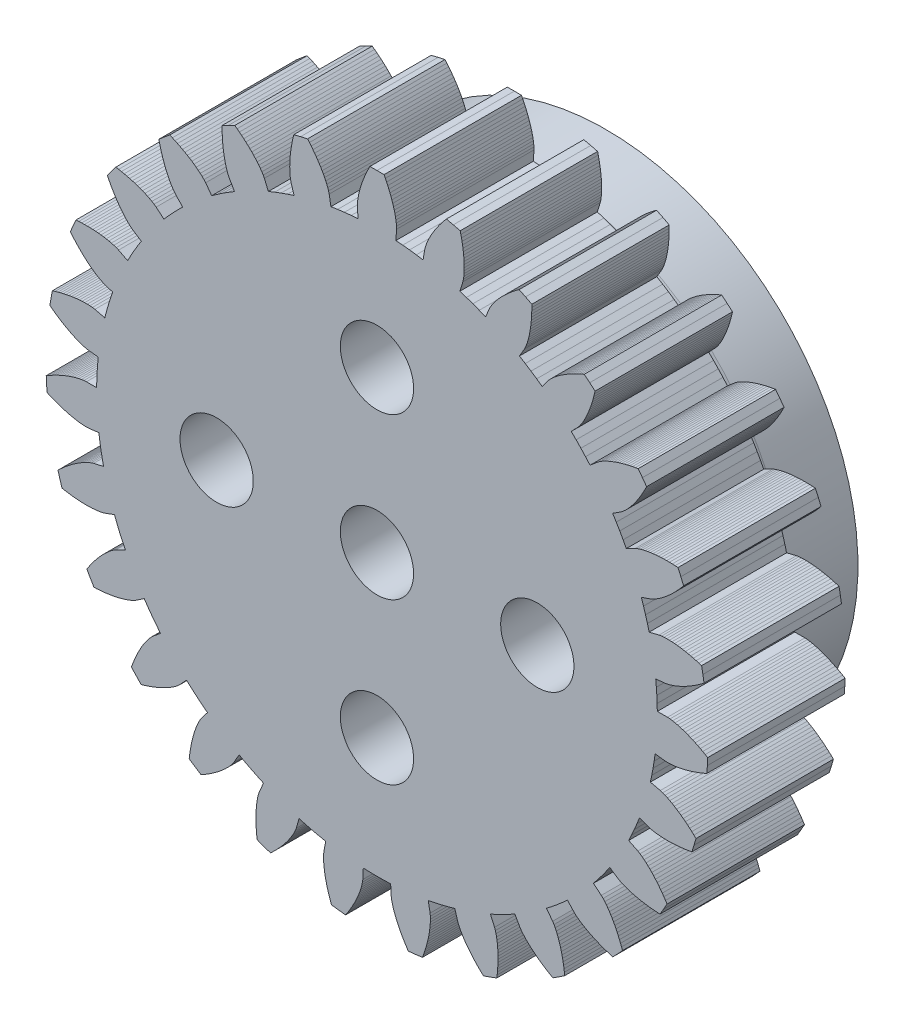
SolidWorks part; units mm, degrees
ref_plane "前视基准面" through (0, 0, 0) normal (0, 0, 1) x (1, 0, 0)
ref_plane "上视基准面" through (0, 0, 0) normal (0, 1, 0) x (1, 0, 0)
ref_plane "右视基准面" through (0, 0, 0) normal (1, 0, 0) x (0, 0, -1)
other "Configuration Table"
sketch "Module 1, 27 teeth, 20 degree pressure angle profile" plane through (0, 0, 0) normal (0, 0, 1) x (1, 0, 0)
  line L0 (1.421, 12.1572) -> (1.1238, 12.1883)
  line L1 (1.1238, 12.1883) -> (0.8259, 12.2121)
  line L2 (0.8259, 12.2121) -> (0.856, 12.6569)
  line L3 (0.856, 12.6569) -> (0.8537, 12.7676)
  line L4 (0.8537, 12.7676) -> (0.8432, 12.8788)
  line L5 (0.8432, 12.8788) -> (0.8273, 12.9903)
  line L6 (0.8273, 12.9903) -> (0.8069, 13.1021)
  line L7 (0.8069, 13.1021) -> (0.7825, 13.214)
  line L8 (0.7825, 13.214) -> (0.7544, 13.3261)
  line L9 (0.7544, 13.3261) -> (0.723, 13.4382)
  line L10 (0.723, 13.4382) -> (0.6884, 13.5505)
  line L11 (0.6884, 13.5505) -> (0.6507, 13.6627)
  line L12 (0.6507, 13.6627) -> (0.6101, 13.7749)
  line L13 (0.6101, 13.7749) -> (0.5666, 13.8871)
  line L14 (0.5666, 13.8871) -> (0.5205, 13.9993)
  line L15 (0.5205, 13.9993) -> (0.4716, 14.1113)
  line L16 (0.4716, 14.1113) -> (0.4202, 14.2233)
  line L17 (0.4202, 14.2233) -> (0.3662, 14.3351)
  line L18 (0.3662, 14.3351) -> (0.3096, 14.4467)
  line L19 (0.3096, 14.4467) -> (0, 14.45)
  line L20 (0, 14.45) -> (-0.3096, 14.4467)
  line L21 (-0.3096, 14.4467) -> (-0.3662, 14.3351)
  line L22 (-0.3662, 14.3351) -> (-0.4202, 14.2233)
  line L23 (-0.4202, 14.2233) -> (-0.4716, 14.1113)
  line L24 (-0.4716, 14.1113) -> (-0.5205, 13.9993)
  line L25 (-0.5205, 13.9993) -> (-0.5666, 13.8871)
  line L26 (-0.5666, 13.8871) -> (-0.6101, 13.7749)
  line L27 (-0.6101, 13.7749) -> (-0.6507, 13.6627)
  line L28 (-0.6507, 13.6627) -> (-0.6884, 13.5505)
  line L29 (-0.6884, 13.5505) -> (-0.723, 13.4382)
  line L30 (-0.723, 13.4382) -> (-0.7544, 13.3261)
  line L31 (-0.7544, 13.3261) -> (-0.7825, 13.214)
  line L32 (-0.7825, 13.214) -> (-0.8069, 13.1021)
  line L33 (-0.8069, 13.1021) -> (-0.8273, 12.9903)
  line L34 (-0.8273, 12.9903) -> (-0.8432, 12.8788)
  line L35 (-0.8432, 12.8788) -> (-0.8537, 12.7676)
  line L36 (-0.8537, 12.7676) -> (-0.856, 12.6569)
  line L37 (-0.856, 12.6569) -> (-0.8259, 12.2121)
  line L38 (-0.8259, 12.2121) -> (-1.1238, 12.1883)
  line L39 (-1.1238, 12.1883) -> (-1.421, 12.1572)
  line L40 (-1.421, 12.1572) -> (-1.7173, 12.1189)
  line L41 (-1.7173, 12.1189) -> (-2.0127, 12.0734)
  line L42 (-2.0127, 12.0734) -> (-2.086, 12.5132)
  line L43 (-2.086, 12.5132) -> (-2.1137, 12.6203)
  line L44 (-2.1137, 12.6203) -> (-2.1495, 12.7261)
  line L45 (-2.1495, 12.7261) -> (-2.1907, 12.831)
  line L46 (-2.1907, 12.831) -> (-2.2364, 12.935)
  line L47 (-2.2364, 12.935) -> (-2.286, 13.0383)
  line L48 (-2.286, 13.0383) -> (-2.3391, 13.1408)
  line L49 (-2.3391, 13.1408) -> (-2.3956, 13.2427)
  line L50 (-2.3956, 13.2427) -> (-2.4551, 13.3439)
  line L51 (-2.4551, 13.3439) -> (-2.5177, 13.4445)
  line L52 (-2.5177, 13.4445) -> (-2.5831, 13.5443)
  line L53 (-2.5831, 13.5443) -> (-2.6512, 13.6435)
  line L54 (-2.6512, 13.6435) -> (-2.722, 13.742)
  line L55 (-2.722, 13.742) -> (-2.7954, 13.8397)
  line L56 (-2.7954, 13.8397) -> (-2.8713, 13.9368)
  line L57 (-2.8713, 13.9368) -> (-2.9496, 14.0331)
  line L58 (-2.9496, 14.0331) -> (-3.0303, 14.1287)
  line L59 (-3.0303, 14.1287) -> (-3.3324, 14.0605)
  line L60 (-3.3324, 14.0605) -> (-3.6329, 13.9859)
  line L61 (-3.6329, 13.9859) -> (-3.6622, 13.8642)
  line L62 (-3.6622, 13.8642) -> (-3.689, 13.743)
  line L63 (-3.689, 13.743) -> (-3.7132, 13.6222)
  line L64 (-3.7132, 13.6222) -> (-3.7349, 13.5019)
  line L65 (-3.7349, 13.5019) -> (-3.754, 13.3821)
  line L66 (-3.754, 13.3821) -> (-3.7704, 13.2629)
  line L67 (-3.7704, 13.2629) -> (-3.784, 13.1444)
  line L68 (-3.784, 13.1444) -> (-3.7948, 13.0264)
  line L69 (-3.7948, 13.0264) -> (-3.8026, 12.9093)
  line L70 (-3.8026, 12.9093) -> (-3.8073, 12.7929)
  line L71 (-3.8073, 12.7929) -> (-3.8088, 12.6774)
  line L72 (-3.8088, 12.6774) -> (-3.8067, 12.5628)
  line L73 (-3.8067, 12.5628) -> (-3.8008, 12.4494)
  line L74 (-3.8008, 12.4494) -> (-3.7906, 12.3372)
  line L75 (-3.7906, 12.3372) -> (-3.7751, 12.2266)
  line L76 (-3.7751, 12.2266) -> (-3.7518, 12.1184)
  line L77 (-3.7518, 12.1184) -> (-3.6199, 11.6925)
  line L78 (-3.6199, 11.6925) -> (-3.9043, 11.6006)
  line L79 (-3.9043, 11.6006) -> (-4.1863, 11.5018)
  line L80 (-4.1863, 11.5018) -> (-4.4659, 11.3962)
  line L81 (-4.4659, 11.3962) -> (-4.7427, 11.2838)
  line L82 (-4.7427, 11.2838) -> (-4.9155, 11.6948)
  line L83 (-4.9155, 11.6948) -> (-4.9672, 11.7927)
  line L84 (-4.9672, 11.7927) -> (-5.0264, 11.8874)
  line L85 (-5.0264, 11.8874) -> (-5.0907, 11.9799)
  line L86 (-5.0907, 11.9799) -> (-5.1591, 12.0706)
  line L87 (-5.1591, 12.0706) -> (-5.2312, 12.1596)
  line L88 (-5.2312, 12.1596) -> (-5.3065, 12.2472)
  line L89 (-5.3065, 12.2472) -> (-5.385, 12.3333)
  line L90 (-5.385, 12.3333) -> (-5.4663, 12.4181)
  line L91 (-5.4663, 12.4181) -> (-5.5503, 12.5015)
  line L92 (-5.5503, 12.5015) -> (-5.637, 12.5835)
  line L93 (-5.637, 12.5835) -> (-5.7262, 12.6643)
  line L94 (-5.7262, 12.6643) -> (-5.8178, 12.7438)
  line L95 (-5.8178, 12.7438) -> (-5.9117, 12.822)
  line L96 (-5.9117, 12.822) -> (-6.0079, 12.899)
  line L97 (-6.0079, 12.899) -> (-6.1064, 12.9746)
  line L98 (-6.1064, 12.9746) -> (-6.207, 13.049)
  line L99 (-6.207, 13.049) -> (-6.4851, 12.913)
  line L100 (-6.4851, 12.913) -> (-6.7604, 12.7711)
  line L101 (-6.7604, 12.7711) -> (-6.7608, 12.646)
  line L102 (-6.7608, 12.646) -> (-6.7589, 12.5218)
  line L103 (-6.7589, 12.5218) -> (-6.7546, 12.3987)
  line L104 (-6.7546, 12.3987) -> (-6.748, 12.2766)
  line L105 (-6.748, 12.2766) -> (-6.7389, 12.1557)
  line L106 (-6.7389, 12.1557) -> (-6.7274, 12.0359)
  line L107 (-6.7274, 12.0359) -> (-6.7133, 11.9174)
  line L108 (-6.7133, 11.9174) -> (-6.6966, 11.8002)
  line L109 (-6.6966, 11.8002) -> (-6.6772, 11.6844)
  line L110 (-6.6772, 11.6844) -> (-6.6549, 11.57)
  line L111 (-6.6549, 11.57) -> (-6.6297, 11.4573)
  line L112 (-6.6297, 11.4573) -> (-6.6013, 11.3463)
  line L113 (-6.6013, 11.3463) -> (-6.5694, 11.2373)
  line L114 (-6.5694, 11.2373) -> (-6.5335, 11.1305)
  line L115 (-6.5335, 11.1305) -> (-6.493, 11.0264)
  line L116 (-6.493, 11.0264) -> (-6.4454, 10.9265)
  line L117 (-6.4454, 10.9265) -> (-6.2188, 10.5425)
  line L118 (-6.2188, 10.5425) -> (-6.4743, 10.3875)
  line L119 (-6.4743, 10.3875) -> (-6.726, 10.2264)
  line L120 (-6.726, 10.2264) -> (-6.9736, 10.0591)
  line L121 (-6.9736, 10.0591) -> (-7.2171, 9.8859)
  line L122 (-7.2171, 9.8859) -> (-7.48, 10.246)
  line L123 (-7.48, 10.246) -> (-7.5529, 10.3293)
  line L124 (-7.5529, 10.3293) -> (-7.6324, 10.4078)
  line L125 (-7.6324, 10.4078) -> (-7.7162, 10.483)
  line L126 (-7.7162, 10.483) -> (-7.8037, 10.5554)
  line L127 (-7.8037, 10.5554) -> (-7.8944, 10.6255)
  line L128 (-7.8944, 10.6255) -> (-7.9879, 10.6933)
  line L129 (-7.9879, 10.6933) -> (-8.0841, 10.759)
  line L130 (-8.0841, 10.759) -> (-8.1827, 10.8227)
  line L131 (-8.1827, 10.8227) -> (-8.2838, 10.8845)
  line L132 (-8.2838, 10.8845) -> (-8.387, 10.9444)
  line L133 (-8.387, 10.9444) -> (-8.4924, 11.0024)
  line L134 (-8.4924, 11.0024) -> (-8.5999, 11.0586)
  line L135 (-8.5999, 11.0586) -> (-8.7093, 11.1131)
  line L136 (-8.7093, 11.1131) -> (-8.8207, 11.1657)
  line L137 (-8.8207, 11.1657) -> (-8.9339, 11.2167)
  line L138 (-8.9339, 11.2167) -> (-9.049, 11.2658)
  line L139 (-9.049, 11.2658) -> (-9.2883, 11.0693)
  line L140 (-9.2883, 11.0693) -> (-9.5233, 10.8678)
  line L141 (-9.5233, 10.8678) -> (-9.4949, 10.7459)
  line L142 (-9.4949, 10.7459) -> (-9.4644, 10.6256)
  line L143 (-9.4644, 10.6256) -> (-9.4319, 10.5068)
  line L144 (-9.4319, 10.5068) -> (-9.3973, 10.3895)
  line L145 (-9.3973, 10.3895) -> (-9.3606, 10.2739)
  line L146 (-9.3606, 10.2739) -> (-9.3217, 10.1601)
  line L147 (-9.3217, 10.1601) -> (-9.2807, 10.048)
  line L148 (-9.2807, 10.048) -> (-9.2374, 9.9378)
  line L149 (-9.2374, 9.9378) -> (-9.1918, 9.8295)
  line L150 (-9.1918, 9.8295) -> (-9.1438, 9.7234)
  line L151 (-9.1438, 9.7234) -> (-9.0932, 9.6195)
  line L152 (-9.0932, 9.6195) -> (-9.04, 9.5181)
  line L153 (-9.04, 9.5181) -> (-8.9838, 9.4194)
  line L154 (-8.9838, 9.4194) -> (-8.9243, 9.3237)
  line L155 (-8.9243, 9.3237) -> (-8.8608, 9.2318)
  line L156 (-8.8608, 9.2318) -> (-8.7914, 9.1456)
  line L157 (-8.7914, 9.1456) -> (-8.4825, 8.8241)
  line L158 (-8.4825, 8.8241) -> (-8.6953, 8.6144)
  line L159 (-8.6953, 8.6144) -> (-8.9031, 8.3996)
  line L160 (-8.9031, 8.3996) -> (-9.1055, 8.1798)
  line L161 (-9.1055, 8.1798) -> (-9.3024, 7.955)
  line L162 (-9.3024, 7.955) -> (-9.6413, 8.2448)
  line L163 (-9.6413, 8.2448) -> (-9.7314, 8.3091)
  line L164 (-9.7314, 8.3091) -> (-9.8268, 8.3671)
  line L165 (-9.8268, 8.3671) -> (-9.9258, 8.4209)
  line L166 (-9.9258, 8.4209) -> (-10.0276, 8.4712)
  line L167 (-10.0276, 8.4712) -> (-10.132, 8.5185)
  line L168 (-10.132, 8.5185) -> (-10.2386, 8.5629)
  line L169 (-10.2386, 8.5629) -> (-10.3474, 8.6047)
  line L170 (-10.3474, 8.6047) -> (-10.4581, 8.6439)
  line L171 (-10.4581, 8.6439) -> (-10.5706, 8.6807)
  line L172 (-10.5706, 8.6807) -> (-10.6849, 8.7152)
  line L173 (-10.6849, 8.7152) -> (-10.8008, 8.7474)
  line L174 (-10.8008, 8.7474) -> (-10.9184, 8.7773)
  line L175 (-10.9184, 8.7773) -> (-11.0374, 8.805)
  line L176 (-11.0374, 8.805) -> (-11.1579, 8.8306)
  line L177 (-11.1579, 8.8306) -> (-11.2798, 8.854)
  line L178 (-11.2798, 8.854) -> (-11.4031, 8.8753)
  line L179 (-11.4031, 8.8753) -> (-11.5907, 8.6289)
  line L180 (-11.5907, 8.6289) -> (-11.7729, 8.3786)
  line L181 (-11.7729, 8.3786) -> (-11.7171, 8.2666)
  line L182 (-11.7171, 8.2666) -> (-11.6597, 8.1565)
  line L183 (-11.6597, 8.1565) -> (-11.6007, 8.0484)
  line L184 (-11.6007, 8.0484) -> (-11.54, 7.9423)
  line L185 (-11.54, 7.9423) -> (-11.4776, 7.8383)
  line L186 (-11.4776, 7.8383) -> (-11.4135, 7.7365)
  line L187 (-11.4135, 7.7365) -> (-11.3477, 7.6369)
  line L188 (-11.3477, 7.6369) -> (-11.2802, 7.5396)
  line L189 (-11.2802, 7.5396) -> (-11.2109, 7.4448)
  line L190 (-11.2109, 7.4448) -> (-11.1397, 7.3526)
  line L191 (-11.1397, 7.3526) -> (-11.0665, 7.2632)
  line L192 (-11.0665, 7.2632) -> (-10.9913, 7.1768)
  line L193 (-10.9913, 7.1768) -> (-10.9139, 7.0937)
  line L194 (-10.9139, 7.0937) -> (-10.8339, 7.0143)
  line L195 (-10.8339, 7.0143) -> (-10.751, 6.9395)
  line L196 (-10.751, 6.9395) -> (-10.6636, 6.8716)
  line L197 (-10.6636, 6.8716) -> (-10.2888, 6.6301)
  line L198 (-10.2888, 6.6301) -> (-10.4476, 6.3769)
  line L199 (-10.4476, 6.3769) -> (-10.6002, 6.12)
  line L200 (-10.6002, 6.12) -> (-10.7464, 5.8594)
  line L201 (-10.7464, 5.8594) -> (-10.8862, 5.5953)
  line L202 (-10.8862, 5.5953) -> (-11.2828, 5.7991)
  line L203 (-11.2828, 5.7991) -> (-11.3853, 5.8409)
  line L204 (-11.3853, 5.8409) -> (-11.4915, 5.8753)
  line L205 (-11.4915, 5.8753) -> (-11.6002, 5.9049)
  line L206 (-11.6002, 5.9049) -> (-11.7109, 5.9304)
  line L207 (-11.7109, 5.9304) -> (-11.8234, 5.9523)
  line L208 (-11.8234, 5.9523) -> (-11.9374, 5.9709)
  line L209 (-11.9374, 5.9709) -> (-12.0528, 5.9865)
  line L210 (-12.0528, 5.9865) -> (-12.1696, 5.9991)
  line L211 (-12.1696, 5.9991) -> (-12.2876, 6.009)
  line L212 (-12.2876, 6.009) -> (-12.4067, 6.0162)
  line L213 (-12.4067, 6.0162) -> (-12.527, 6.0207)
  line L214 (-12.527, 6.0207) -> (-12.6482, 6.0227)
  line L215 (-12.6482, 6.0227) -> (-12.7705, 6.0223)
  line L216 (-12.7705, 6.0223) -> (-12.8936, 6.0194)
  line L217 (-12.8936, 6.0194) -> (-13.0177, 6.014)
  line L218 (-13.0177, 6.014) -> (-13.1425, 6.0064)
  line L219 (-13.1425, 6.0064) -> (-13.2682, 5.7234)
  line L220 (-13.2682, 5.7234) -> (-13.3878, 5.4377)
  line L221 (-13.3878, 5.4377) -> (-13.3077, 5.3416)
  line L222 (-13.3077, 5.3416) -> (-13.2265, 5.2477)
  line L223 (-13.2265, 5.2477) -> (-13.1441, 5.1562)
  line L224 (-13.1441, 5.1562) -> (-13.0605, 5.0669)
  line L225 (-13.0605, 5.0669) -> (-12.9758, 4.9801)
  line L226 (-12.9758, 4.9801) -> (-12.89, 4.8958)
  line L227 (-12.89, 4.8958) -> (-12.803, 4.814)
  line L228 (-12.803, 4.814) -> (-12.7149, 4.735)
  line L229 (-12.7149, 4.735) -> (-12.6256, 4.6587)
  line L230 (-12.6256, 4.6587) -> (-12.535, 4.5855)
  line L231 (-12.535, 4.5855) -> (-12.4432, 4.5153)
  line L232 (-12.4432, 4.5153) -> (-12.3501, 4.4486)
  line L233 (-12.3501, 4.4486) -> (-12.2556, 4.3855)
  line L234 (-12.2556, 4.3855) -> (-12.1595, 4.3267)
  line L235 (-12.1595, 4.3267) -> (-12.0616, 4.2731)
  line L236 (-12.0616, 4.2731) -> (-11.9608, 4.2272)
  line L237 (-11.9608, 4.2272) -> (-11.5405, 4.0786)
  line L238 (-11.5405, 4.0786) -> (-11.6366, 3.7957)
  line L239 (-11.6366, 3.7957) -> (-11.7258, 3.5105)
  line L240 (-11.7258, 3.5105) -> (-11.808, 3.2232)
  line L241 (-11.808, 3.2232) -> (-11.8832, 2.934)
  line L242 (-11.8832, 2.934) -> (-12.316, 3.0408)
  line L243 (-12.316, 3.0408) -> (-12.4254, 3.0578)
  line L244 (-12.4254, 3.0578) -> (-12.5367, 3.0668)
  line L245 (-12.5367, 3.0668) -> (-12.6493, 3.0705)
  line L246 (-12.6493, 3.0705) -> (-12.7629, 3.0698)
  line L247 (-12.7629, 3.0698) -> (-12.8774, 3.0652)
  line L248 (-12.8774, 3.0652) -> (-12.9926, 3.057)
  line L249 (-12.9926, 3.057) -> (-13.1085, 3.0455)
  line L250 (-13.1085, 3.0455) -> (-13.2251, 3.0309)
  line L251 (-13.2251, 3.0309) -> (-13.3421, 3.0133)
  line L252 (-13.3421, 3.0133) -> (-13.4597, 2.9928)
  line L253 (-13.4597, 2.9928) -> (-13.5778, 2.9695)
  line L254 (-13.5778, 2.9695) -> (-13.6962, 2.9435)
  line L255 (-13.6962, 2.9435) -> (-13.8151, 2.9149)
  line L256 (-13.8151, 2.9149) -> (-13.9342, 2.8836)
  line L257 (-13.9342, 2.8836) -> (-14.0537, 2.8499)
  line L258 (-14.0537, 2.8499) -> (-14.1734, 2.8136)
  line L259 (-14.1734, 2.8136) -> (-14.2305, 2.5092)
  line L260 (-14.2305, 2.5092) -> (-14.281, 2.2037)
  line L261 (-14.281, 2.2037) -> (-14.1809, 2.1287)
  line L262 (-14.1809, 2.1287) -> (-14.0802, 2.0561)
  line L263 (-14.0802, 2.0561) -> (-13.9789, 1.9859)
  line L264 (-13.9789, 1.9859) -> (-13.877, 1.9184)
  line L265 (-13.877, 1.9184) -> (-13.7746, 1.8534)
  line L266 (-13.7746, 1.8534) -> (-13.6716, 1.7912)
  line L267 (-13.6716, 1.7912) -> (-13.5681, 1.7317)
  line L268 (-13.5681, 1.7317) -> (-13.4641, 1.6751)
  line L269 (-13.4641, 1.6751) -> (-13.3596, 1.6215)
  line L270 (-13.3596, 1.6215) -> (-13.2546, 1.5711)
  line L271 (-13.2546, 1.5711) -> (-13.1491, 1.524)
  line L272 (-13.1491, 1.524) -> (-13.0431, 1.4805)
  line L273 (-13.0431, 1.4805) -> (-12.9366, 1.441)
  line L274 (-12.9366, 1.441) -> (-12.8296, 1.4059)
  line L275 (-12.8296, 1.4059) -> (-12.7219, 1.3763)
  line L276 (-12.7219, 1.3763) -> (-12.6133, 1.3549)
  line L277 (-12.6133, 1.3549) -> (-12.17, 1.3073)
  line L278 (-12.17, 1.3073) -> (-12.1983, 1.0098)
  line L279 (-12.1983, 1.0098) -> (-12.2193, 0.7117)
  line L280 (-12.2193, 0.7117) -> (-12.233, 0.4132)
  line L281 (-12.233, 0.4132) -> (-12.2395, 0.1144)
  line L282 (-12.2395, 0.1144) -> (-12.6853, 0.1186)
  line L283 (-12.6853, 0.1186) -> (-12.7956, 0.1099)
  line L284 (-12.7956, 0.1099) -> (-12.906, 0.093)
  line L285 (-12.906, 0.093) -> (-13.0164, 0.0706)
  line L286 (-13.0164, 0.0706) -> (-13.1268, 0.0437)
  line L287 (-13.1268, 0.0437) -> (-13.2371, 0.0128)
  line L288 (-13.2371, 0.0128) -> (-13.3474, -0.0217)
  line L289 (-13.3474, -0.0217) -> (-13.4575, -0.0596)
  line L290 (-13.4575, -0.0596) -> (-13.5676, -0.1007)
  line L291 (-13.5676, -0.1007) -> (-13.6774, -0.1448)
  line L292 (-13.6774, -0.1448) -> (-13.7871, -0.1919)
  line L293 (-13.7871, -0.1919) -> (-13.8966, -0.2418)
  line L294 (-13.8966, -0.2418) -> (-14.0059, -0.2944)
  line L295 (-14.0059, -0.2944) -> (-14.1149, -0.3497)
  line L296 (-14.1149, -0.3497) -> (-14.2236, -0.4076)
  line L297 (-14.2236, -0.4076) -> (-14.3321, -0.468)
  line L298 (-14.3321, -0.468) -> (-14.4402, -0.5309)
  line L299 (-14.4402, -0.5309) -> (-14.4256, -0.8402)
  line L300 (-14.4256, -0.8402) -> (-14.4042, -1.1491)
  line L301 (-14.4042, -1.1491) -> (-14.2895, -1.199)
  line L302 (-14.2895, -1.199) -> (-14.1748, -1.2465)
  line L303 (-14.1748, -1.2465) -> (-14.06, -1.2913)
  line L304 (-14.06, -1.2913) -> (-13.9453, -1.3336)
  line L305 (-13.9453, -1.3336) -> (-13.8307, -1.3732)
  line L306 (-13.8307, -1.3732) -> (-13.7162, -1.41)
  line L307 (-13.7162, -1.41) -> (-13.6017, -1.444)
  line L308 (-13.6017, -1.444) -> (-13.4875, -1.4751)
  line L309 (-13.4875, -1.4751) -> (-13.3735, -1.5031)
  line L310 (-13.3735, -1.5031) -> (-13.2597, -1.528)
  line L311 (-13.2597, -1.528) -> (-13.1461, -1.5495)
  line L312 (-13.1461, -1.5495) -> (-13.033, -1.5674)
  line L313 (-13.033, -1.5674) -> (-12.9202, -1.5813)
  line L314 (-12.9202, -1.5813) -> (-12.808, -1.5907)
  line L315 (-12.808, -1.5907) -> (-12.6964, -1.5946)
  line L316 (-12.6964, -1.5946) -> (-12.5858, -1.5905)
  line L317 (-12.5858, -1.5905) -> (-12.1434, -1.5346)
  line L318 (-12.1434, -1.5346) -> (-12.1023, -1.8306)
  line L319 (-12.1023, -1.8306) -> (-12.054, -2.1255)
  line L320 (-12.054, -2.1255) -> (-11.9986, -2.4191)
  line L321 (-11.9986, -2.4191) -> (-11.9359, -2.7113)
  line L322 (-11.9359, -2.7113) -> (-12.3707, -2.81)
  line L323 (-12.3707, -2.81) -> (-12.4761, -2.8439)
  line L324 (-12.4761, -2.8439) -> (-12.5796, -2.8859)
  line L325 (-12.5796, -2.8859) -> (-12.6819, -2.9331)
  line L326 (-12.6819, -2.9331) -> (-12.7831, -2.9847)
  line L327 (-12.7831, -2.9847) -> (-12.8833, -3.0402)
  line L328 (-12.8833, -3.0402) -> (-12.9826, -3.0992)
  line L329 (-12.9826, -3.0992) -> (-13.081, -3.1615)
  line L330 (-13.081, -3.1615) -> (-13.1786, -3.2269)
  line L331 (-13.1786, -3.2269) -> (-13.2753, -3.2952)
  line L332 (-13.2753, -3.2952) -> (-13.3712, -3.3662)
  line L333 (-13.3712, -3.3662) -> (-13.4663, -3.44)
  line L334 (-13.4663, -3.44) -> (-13.5604, -3.5164)
  line L335 (-13.5604, -3.5164) -> (-13.6538, -3.5954)
  line L336 (-13.6538, -3.5954) -> (-13.7463, -3.6768)
  line L337 (-13.7463, -3.6768) -> (-13.8379, -3.7606)
  line L338 (-13.8379, -3.7606) -> (-13.9286, -3.8467)
  line L339 (-13.9286, -3.8467) -> (-13.8429, -4.1443)
  line L340 (-13.8429, -4.1443) -> (-13.751, -4.44)
  line L341 (-13.751, -4.44) -> (-13.6278, -4.4621)
  line L342 (-13.6278, -4.4621) -> (-13.5052, -4.4818)
  line L343 (-13.5052, -4.4818) -> (-13.3833, -4.499)
  line L344 (-13.3833, -4.499) -> (-13.2619, -4.5136)
  line L345 (-13.2619, -4.5136) -> (-13.1412, -4.5257)
  line L346 (-13.1412, -4.5257) -> (-13.0213, -4.5351)
  line L347 (-13.0213, -4.5351) -> (-12.9021, -4.5419)
  line L348 (-12.9021, -4.5419) -> (-12.7838, -4.5458)
  line L349 (-12.7838, -4.5458) -> (-12.6663, -4.5468)
  line L350 (-12.6663, -4.5468) -> (-12.5499, -4.5447)
  line L351 (-12.5499, -4.5447) -> (-12.4345, -4.5394)
  line L352 (-12.4345, -4.5394) -> (-12.3202, -4.5307)
  line L353 (-12.3202, -4.5307) -> (-12.2073, -4.5182)
  line L354 (-12.2073, -4.5182) -> (-12.0959, -4.5015)
  line L355 (-12.0959, -4.5015) -> (-11.9864, -4.4796)
  line L356 (-11.9864, -4.4796) -> (-11.8797, -4.4501)
  line L357 (-11.8797, -4.4501) -> (-11.4622, -4.2937)
  line L358 (-11.4622, -4.2937) -> (-11.354, -4.5722)
  line L359 (-11.354, -4.5722) -> (-11.239, -4.848)
  line L360 (-11.239, -4.848) -> (-11.1173, -5.1209)
  line L361 (-11.1173, -5.1209) -> (-10.9889, -5.3908)
  line L362 (-10.9889, -5.3908) -> (-11.3892, -5.5872)
  line L363 (-11.3892, -5.5872) -> (-11.4839, -5.6445)
  line L364 (-11.4839, -5.6445) -> (-11.575, -5.7091)
  line L365 (-11.575, -5.7091) -> (-11.6636, -5.7787)
  line L366 (-11.6636, -5.7787) -> (-11.7502, -5.8522)
  line L367 (-11.7502, -5.8522) -> (-11.8349, -5.9293)
  line L368 (-11.8349, -5.9293) -> (-11.9179, -6.0097)
  line L369 (-11.9179, -6.0097) -> (-11.9993, -6.093)
  line L370 (-11.9993, -6.093) -> (-12.0792, -6.1791)
  line L371 (-12.0792, -6.1791) -> (-12.1576, -6.2678)
  line L372 (-12.1576, -6.2678) -> (-12.2345, -6.3591)
  line L373 (-12.2345, -6.3591) -> (-12.3099, -6.4528)
  line L374 (-12.3099, -6.4528) -> (-12.384, -6.5489)
  line L375 (-12.384, -6.5489) -> (-12.4566, -6.6472)
  line L376 (-12.4566, -6.6472) -> (-12.5278, -6.7478)
  line L377 (-12.5278, -6.7478) -> (-12.5976, -6.8504)
  line L378 (-12.5976, -6.8504) -> (-12.666, -6.9552)
  line L379 (-12.666, -6.9552) -> (-12.5141, -7.225)
  line L380 (-12.5141, -7.225) -> (-12.3564, -7.4915)
  line L381 (-12.3564, -7.4915) -> (-12.2315, -7.4846)
  line L382 (-12.2315, -7.4846) -> (-12.1076, -7.4755)
  line L383 (-12.1076, -7.4755) -> (-11.985, -7.4641)
  line L384 (-11.985, -7.4641) -> (-11.8635, -7.4504)
  line L385 (-11.8635, -7.4504) -> (-11.7433, -7.4343)
  line L386 (-11.7433, -7.4343) -> (-11.6244, -7.4158)
  line L387 (-11.6244, -7.4158) -> (-11.5069, -7.3949)
  line L388 (-11.5069, -7.3949) -> (-11.3909, -7.3714)
  line L389 (-11.3909, -7.3714) -> (-11.2763, -7.3453)
  line L390 (-11.2763, -7.3453) -> (-11.1635, -7.3164)
  line L391 (-11.1635, -7.3164) -> (-11.0524, -7.2847)
  line L392 (-11.0524, -7.2847) -> (-10.9433, -7.2498)
  line L393 (-10.9433, -7.2498) -> (-10.8363, -7.2116)
  line L394 (-10.8363, -7.2116) -> (-10.7317, -7.1697)
  line L395 (-10.7317, -7.1697) -> (-10.6302, -7.1231)
  line L396 (-10.6302, -7.1231) -> (-10.5332, -7.0698)
  line L397 (-10.5332, -7.0698) -> (-10.163, -6.8213)
  line L398 (-10.163, -6.8213) -> (-9.9935, -7.0674)
  line L399 (-9.9935, -7.0674) -> (-9.818, -7.3092)
  line L400 (-9.818, -7.3092) -> (-9.6366, -7.5467)
  line L401 (-9.6366, -7.5467) -> (-9.4495, -7.7797)
  line L402 (-9.4495, -7.7797) -> (-9.7937, -8.0631)
  line L403 (-9.7937, -8.0631) -> (-9.8727, -8.1407)
  line L404 (-9.8727, -8.1407) -> (-9.9464, -8.2246)
  line L405 (-9.9464, -8.2246) -> (-10.0166, -8.3127)
  line L406 (-10.0166, -8.3127) -> (-10.0838, -8.4043)
  line L407 (-10.0838, -8.4043) -> (-10.1485, -8.4988)
  line L408 (-10.1485, -8.4988) -> (-10.2108, -8.5961)
  line L409 (-10.2108, -8.5961) -> (-10.2708, -8.696)
  line L410 (-10.2708, -8.696) -> (-10.3286, -8.7982)
  line L411 (-10.3286, -8.7982) -> (-10.3844, -8.9026)
  line L412 (-10.3844, -8.9026) -> (-10.4382, -9.0092)
  line L413 (-10.4382, -9.0092) -> (-10.49, -9.1178)
  line L414 (-10.49, -9.1178) -> (-10.5399, -9.2283)
  line L415 (-10.5399, -9.2283) -> (-10.5879, -9.3407)
  line L416 (-10.5879, -9.3407) -> (-10.634, -9.455)
  line L417 (-10.634, -9.455) -> (-10.6782, -9.571)
  line L418 (-10.6782, -9.571) -> (-10.7206, -9.6887)
  line L419 (-10.7206, -9.6887) -> (-10.5105, -9.9162)
  line L420 (-10.5105, -9.9162) -> (-10.2957, -10.1391)
  line L421 (-10.2957, -10.1391) -> (-10.1757, -10.1037)
  line L422 (-10.1757, -10.1037) -> (-10.0573, -10.0662)
  line L423 (-10.0573, -10.0662) -> (-9.9406, -10.0268)
  line L424 (-9.9406, -10.0268) -> (-9.8255, -9.9855)
  line L425 (-9.8255, -9.9855) -> (-9.7123, -9.9421)
  line L426 (-9.7123, -9.9421) -> (-9.6009, -9.8967)
  line L427 (-9.6009, -9.8967) -> (-9.4914, -9.8492)
  line L428 (-9.4914, -9.8492) -> (-9.3839, -9.7996)
  line L429 (-9.3839, -9.7996) -> (-9.2785, -9.7478)
  line L430 (-9.2785, -9.7478) -> (-9.1753, -9.6937)
  line L431 (-9.1753, -9.6937) -> (-9.0745, -9.6372)
  line L432 (-9.0745, -9.6372) -> (-8.9764, -9.5781)
  line L433 (-8.9764, -9.5781) -> (-8.8811, -9.5163)
  line L434 (-8.8811, -9.5163) -> (-8.789, -9.4513)
  line L435 (-8.789, -9.4513) -> (-8.701, -9.3826)
  line L436 (-8.701, -9.3826) -> (-8.6189, -9.3083)
  line L437 (-8.6189, -9.3083) -> (-8.316, -8.9812)
  line L438 (-8.316, -8.9812) -> (-8.0943, -9.1815)
  line L439 (-8.0943, -9.1815) -> (-7.8677, -9.3764)
  line L440 (-7.8677, -9.3764) -> (-7.6365, -9.5657)
  line L441 (-7.6365, -9.5657) -> (-7.4007, -9.7492)
  line L442 (-7.4007, -9.7492) -> (-7.6703, -10.1043)
  line L443 (-7.6703, -10.1043) -> (-7.7292, -10.1981)
  line L444 (-7.7292, -10.1981) -> (-7.7815, -10.2967)
  line L445 (-7.7815, -10.2967) -> (-7.8295, -10.3986)
  line L446 (-7.8295, -10.3986) -> (-7.8739, -10.5032)
  line L447 (-7.8739, -10.5032) -> (-7.915, -10.6102)
  line L448 (-7.915, -10.6102) -> (-7.9531, -10.7192)
  line L449 (-7.9531, -10.7192) -> (-7.9885, -10.8302)
  line L450 (-7.9885, -10.8302) -> (-8.0212, -10.943)
  line L451 (-8.0212, -10.943) -> (-8.0514, -11.0575)
  line L452 (-8.0514, -11.0575) -> (-8.0792, -11.1735)
  line L453 (-8.0792, -11.1735) -> (-8.1045, -11.2912)
  line L454 (-8.1045, -11.2912) -> (-8.1276, -11.4102)
  line L455 (-8.1276, -11.4102) -> (-8.1483, -11.5307)
  line L456 (-8.1483, -11.5307) -> (-8.1669, -11.6525)
  line L457 (-8.1669, -11.6525) -> (-8.1832, -11.7756)
  line L458 (-8.1832, -11.7756) -> (-8.1973, -11.8999)
  line L459 (-8.1973, -11.8999) -> (-7.9404, -12.0728)
  line L460 (-7.9404, -12.0728) -> (-7.6799, -12.2402)
  line L461 (-7.6799, -12.2402) -> (-7.5713, -12.178)
  line L462 (-7.5713, -12.178) -> (-7.4648, -12.1143)
  line L463 (-7.4648, -12.1143) -> (-7.3603, -12.049)
  line L464 (-7.3603, -12.049) -> (-7.2579, -11.9822)
  line L465 (-7.2579, -11.9822) -> (-7.1577, -11.9139)
  line L466 (-7.1577, -11.9139) -> (-7.0597, -11.844)
  line L467 (-7.0597, -11.844) -> (-6.9641, -11.7726)
  line L468 (-6.9641, -11.7726) -> (-6.871, -11.6995)
  line L469 (-6.871, -11.6995) -> (-6.7804, -11.6248)
  line L470 (-6.7804, -11.6248) -> (-6.6925, -11.5483)
  line L471 (-6.6925, -11.5483) -> (-6.6075, -11.4701)
  line L472 (-6.6075, -11.4701) -> (-6.5255, -11.39)
  line L473 (-6.5255, -11.39) -> (-6.4471, -11.3079)
  line L474 (-6.4471, -11.3079) -> (-6.3725, -11.2234)
  line L475 (-6.3725, -11.2234) -> (-6.3027, -11.1363)
  line L476 (-6.3027, -11.1363) -> (-6.2399, -11.0451)
  line L477 (-6.2399, -11.0451) -> (-6.0206, -10.6569)
  line L478 (-6.0206, -10.6569) -> (-5.7587, -10.8007)
  line L479 (-5.7587, -10.8007) -> (-5.4933, -10.9381)
  line L480 (-5.4933, -10.9381) -> (-5.2246, -11.0689)
  line L481 (-5.2246, -11.0689) -> (-4.9529, -11.1932)
  line L482 (-4.9529, -11.1932) -> (-5.1333, -11.6009)
  line L483 (-5.1333, -11.6009) -> (-5.169, -11.7056)
  line L484 (-5.169, -11.7056) -> (-5.1972, -11.8137)
  line L485 (-5.1972, -11.8137) -> (-5.2204, -11.9239)
  line L486 (-5.2204, -11.9239) -> (-5.2394, -12.0359)
  line L487 (-5.2394, -12.0359) -> (-5.2548, -12.1495)
  line L488 (-5.2548, -12.1495) -> (-5.2667, -12.2644)
  line L489 (-5.2667, -12.2644) -> (-5.2755, -12.3805)
  line L490 (-5.2755, -12.3805) -> (-5.2814, -12.4978)
  line L491 (-5.2814, -12.4978) -> (-5.2844, -12.6162)
  line L492 (-5.2844, -12.6162) -> (-5.2846, -12.7355)
  line L493 (-5.2846, -12.7355) -> (-5.2822, -12.8558)
  line L494 (-5.2822, -12.8558) -> (-5.2771, -12.977)
  line L495 (-5.2771, -12.977) -> (-5.2695, -13.099)
  line L496 (-5.2695, -13.099) -> (-5.2595, -13.2218)
  line L497 (-5.2595, -13.2218) -> (-5.247, -13.3453)
  line L498 (-5.247, -13.3453) -> (-5.232, -13.4695)
  line L499 (-5.232, -13.4695) -> (-4.9422, -13.5786)
  line L500 (-4.9422, -13.5786) -> (-4.6501, -13.6813)
  line L501 (-4.6501, -13.6813) -> (-4.5588, -13.5958)
  line L502 (-4.5588, -13.5958) -> (-4.4698, -13.5092)
  line L503 (-4.4698, -13.5092) -> (-4.3832, -13.4216)
  line L504 (-4.3832, -13.4216) -> (-4.299, -13.333)
  line L505 (-4.299, -13.333) -> (-4.2172, -13.2435)
  line L506 (-4.2172, -13.2435) -> (-4.138, -13.1529)
  line L507 (-4.138, -13.1529) -> (-4.0615, -13.0613)
  line L508 (-4.0615, -13.0613) -> (-3.9877, -12.9687)
  line L509 (-3.9877, -12.9687) -> (-3.9167, -12.8751)
  line L510 (-3.9167, -12.8751) -> (-3.8488, -12.7804)
  line L511 (-3.8488, -12.7804) -> (-3.7842, -12.6847)
  line L512 (-3.7842, -12.6847) -> (-3.7229, -12.5879)
  line L513 (-3.7229, -12.5879) -> (-3.6655, -12.4899)
  line L514 (-3.6655, -12.4899) -> (-3.6124, -12.3905)
  line L515 (-3.6124, -12.3905) -> (-3.5646, -12.2896)
  line L516 (-3.5646, -12.2896) -> (-3.5246, -12.1864)
  line L517 (-3.5246, -12.1864) -> (-3.4007, -11.7581)
  line L518 (-3.4007, -11.7581) -> (-3.1126, -11.8376)
  line L519 (-3.1126, -11.8376) -> (-2.8227, -11.9101)
  line L520 (-2.8227, -11.9101) -> (-2.5311, -11.9754)
  line L521 (-2.5311, -11.9754) -> (-2.2381, -12.0336)
  line L522 (-2.2381, -12.0336) -> (-2.3196, -12.472)
  line L523 (-2.3196, -12.472) -> (-2.3302, -12.5822)
  line L524 (-2.3302, -12.5822) -> (-2.3327, -12.6938)
  line L525 (-2.3327, -12.6938) -> (-2.3298, -12.8064)
  line L526 (-2.3298, -12.8064) -> (-2.3225, -12.9198)
  line L527 (-2.3225, -12.9198) -> (-2.3112, -13.0338)
  line L528 (-2.3112, -13.0338) -> (-2.2964, -13.1484)
  line L529 (-2.2964, -13.1484) -> (-2.2782, -13.2634)
  line L530 (-2.2782, -13.2634) -> (-2.2568, -13.3789)
  line L531 (-2.2568, -13.3789) -> (-2.2324, -13.4948)
  line L532 (-2.2324, -13.4948) -> (-2.2051, -13.611)
  line L533 (-2.2051, -13.611) -> (-2.175, -13.7275)
  line L534 (-2.175, -13.7275) -> (-2.1422, -13.8442)
  line L535 (-2.1422, -13.8442) -> (-2.1067, -13.9612)
  line L536 (-2.1067, -13.9612) -> (-2.0686, -14.0783)
  line L537 (-2.0686, -14.0783) -> (-2.0279, -14.1956)
  line L538 (-2.0279, -14.1956) -> (-1.9847, -14.3131)
  line L539 (-1.9847, -14.3131) -> (-1.6775, -14.3523)
  line L540 (-1.6775, -14.3523) -> (-1.3696, -14.3849)
  line L541 (-1.3696, -14.3849) -> (-1.3005, -14.2806)
  line L542 (-1.3005, -14.2806) -> (-1.2339, -14.1759)
  line L543 (-1.2339, -14.1759) -> (-1.1698, -14.0707)
  line L544 (-1.1698, -14.0707) -> (-1.1083, -13.9651)
  line L545 (-1.1083, -13.9651) -> (-1.0494, -13.859)
  line L546 (-1.0494, -13.859) -> (-0.9932, -13.7526)
  line L547 (-0.9932, -13.7526) -> (-0.9399, -13.6459)
  line L548 (-0.9399, -13.6459) -> (-0.8894, -13.5387)
  line L549 (-0.8894, -13.5387) -> (-0.842, -13.4313)
  line L550 (-0.842, -13.4313) -> (-0.7977, -13.3235)
  line L551 (-0.7977, -13.3235) -> (-0.7569, -13.2155)
  line L552 (-0.7569, -13.2155) -> (-0.7196, -13.1071)
  line L553 (-0.7196, -13.1071) -> (-0.6863, -12.9985)
  line L554 (-0.6863, -12.9985) -> (-0.6576, -12.8896)
  line L555 (-0.6576, -12.8896) -> (-0.6343, -12.7804)
  line L556 (-0.6343, -12.7804) -> (-0.6192, -12.6707)
  line L557 (-0.6192, -12.6707) -> (-0.5974, -12.2254)
  line L558 (-0.5974, -12.2254) -> (-0.2988, -12.2364)
  line L559 (-0.2988, -12.2364) -> (0, -12.24)
  line L560 (0, -12.24) -> (0.2988, -12.2364)
  line L561 (0.2988, -12.2364) -> (0.5974, -12.2254)
  line L562 (0.5974, -12.2254) -> (0.6192, -12.6707)
  line L563 (0.6192, -12.6707) -> (0.6343, -12.7804)
  line L564 (0.6343, -12.7804) -> (0.6576, -12.8896)
  line L565 (0.6576, -12.8896) -> (0.6863, -12.9985)
  line L566 (0.6863, -12.9985) -> (0.7196, -13.1071)
  line L567 (0.7196, -13.1071) -> (0.7569, -13.2155)
  line L568 (0.7569, -13.2155) -> (0.7977, -13.3235)
  line L569 (0.7977, -13.3235) -> (0.842, -13.4313)
  line L570 (0.842, -13.4313) -> (0.8894, -13.5387)
  line L571 (0.8894, -13.5387) -> (0.9399, -13.6459)
  line L572 (0.9399, -13.6459) -> (0.9932, -13.7526)
  line L573 (0.9932, -13.7526) -> (1.0494, -13.859)
  line L574 (1.0494, -13.859) -> (1.1083, -13.9651)
  line L575 (1.1083, -13.9651) -> (1.1698, -14.0707)
  line L576 (1.1698, -14.0707) -> (1.2339, -14.1759)
  line L577 (1.2339, -14.1759) -> (1.3005, -14.2806)
  line L578 (1.3005, -14.2806) -> (1.3696, -14.3849)
  line L579 (1.3696, -14.3849) -> (1.6775, -14.3523)
  line L580 (1.6775, -14.3523) -> (1.9847, -14.3131)
  line L581 (1.9847, -14.3131) -> (2.0279, -14.1956)
  line L582 (2.0279, -14.1956) -> (2.0686, -14.0783)
  line L583 (2.0686, -14.0783) -> (2.1067, -13.9612)
  line L584 (2.1067, -13.9612) -> (2.1422, -13.8442)
  line L585 (2.1422, -13.8442) -> (2.175, -13.7275)
  line L586 (2.175, -13.7275) -> (2.2051, -13.611)
  line L587 (2.2051, -13.611) -> (2.2324, -13.4948)
  line L588 (2.2324, -13.4948) -> (2.2568, -13.3789)
  line L589 (2.2568, -13.3789) -> (2.2782, -13.2634)
  line L590 (2.2782, -13.2634) -> (2.2964, -13.1484)
  line L591 (2.2964, -13.1484) -> (2.3112, -13.0338)
  line L592 (2.3112, -13.0338) -> (2.3225, -12.9198)
  line L593 (2.3225, -12.9198) -> (2.3298, -12.8064)
  line L594 (2.3298, -12.8064) -> (2.3327, -12.6938)
  line L595 (2.3327, -12.6938) -> (2.3302, -12.5822)
  line L596 (2.3302, -12.5822) -> (2.3196, -12.472)
  line L597 (2.3196, -12.472) -> (2.2381, -12.0336)
  line L598 (2.2381, -12.0336) -> (2.5311, -11.9754)
  line L599 (2.5311, -11.9754) -> (2.8227, -11.9101)
  line L600 (2.8227, -11.9101) -> (3.1126, -11.8376)
  line L601 (3.1126, -11.8376) -> (3.4007, -11.7581)
  line L602 (3.4007, -11.7581) -> (3.5246, -12.1864)
  line L603 (3.5246, -12.1864) -> (3.5646, -12.2896)
  line L604 (3.5646, -12.2896) -> (3.6124, -12.3905)
  line L605 (3.6124, -12.3905) -> (3.6655, -12.4899)
  line L606 (3.6655, -12.4899) -> (3.7229, -12.5879)
  line L607 (3.7229, -12.5879) -> (3.7842, -12.6847)
  line L608 (3.7842, -12.6847) -> (3.8488, -12.7804)
  line L609 (3.8488, -12.7804) -> (3.9167, -12.8751)
  line L610 (3.9167, -12.8751) -> (3.9877, -12.9687)
  line L611 (3.9877, -12.9687) -> (4.0615, -13.0613)
  line L612 (4.0615, -13.0613) -> (4.138, -13.1529)
  line L613 (4.138, -13.1529) -> (4.2172, -13.2435)
  line L614 (4.2172, -13.2435) -> (4.299, -13.333)
  line L615 (4.299, -13.333) -> (4.3832, -13.4216)
  line L616 (4.3832, -13.4216) -> (4.4698, -13.5092)
  line L617 (4.4698, -13.5092) -> (4.5588, -13.5958)
  line L618 (4.5588, -13.5958) -> (4.6501, -13.6813)
  line L619 (4.6501, -13.6813) -> (4.9422, -13.5786)
  line L620 (4.9422, -13.5786) -> (5.232, -13.4695)
  line L621 (5.232, -13.4695) -> (5.247, -13.3453)
  line L622 (5.247, -13.3453) -> (5.2595, -13.2218)
  line L623 (5.2595, -13.2218) -> (5.2695, -13.099)
  line L624 (5.2695, -13.099) -> (5.2771, -12.977)
  line L625 (5.2771, -12.977) -> (5.2822, -12.8558)
  line L626 (5.2822, -12.8558) -> (5.2846, -12.7355)
  line L627 (5.2846, -12.7355) -> (5.2844, -12.6162)
  line L628 (5.2844, -12.6162) -> (5.2814, -12.4978)
  line L629 (5.2814, -12.4978) -> (5.2755, -12.3805)
  line L630 (5.2755, -12.3805) -> (5.2667, -12.2644)
  line L631 (5.2667, -12.2644) -> (5.2548, -12.1495)
  line L632 (5.2548, -12.1495) -> (5.2394, -12.0359)
  line L633 (5.2394, -12.0359) -> (5.2204, -11.9239)
  line L634 (5.2204, -11.9239) -> (5.1972, -11.8137)
  line L635 (5.1972, -11.8137) -> (5.169, -11.7056)
  line L636 (5.169, -11.7056) -> (5.1333, -11.6009)
  line L637 (5.1333, -11.6009) -> (4.9529, -11.1932)
  line L638 (4.9529, -11.1932) -> (5.2246, -11.0689)
  line L639 (5.2246, -11.0689) -> (5.4933, -10.9381)
  line L640 (5.4933, -10.9381) -> (5.7587, -10.8007)
  line L641 (5.7587, -10.8007) -> (6.0206, -10.6569)
  line L642 (6.0206, -10.6569) -> (6.2399, -11.0451)
  line L643 (6.2399, -11.0451) -> (6.3027, -11.1363)
  line L644 (6.3027, -11.1363) -> (6.3725, -11.2234)
  line L645 (6.3725, -11.2234) -> (6.4471, -11.3079)
  line L646 (6.4471, -11.3079) -> (6.5255, -11.39)
  line L647 (6.5255, -11.39) -> (6.6075, -11.4701)
  line L648 (6.6075, -11.4701) -> (6.6925, -11.5483)
  line L649 (6.6925, -11.5483) -> (6.7804, -11.6248)
  line L650 (6.7804, -11.6248) -> (6.871, -11.6995)
  line L651 (6.871, -11.6995) -> (6.9641, -11.7726)
  line L652 (6.9641, -11.7726) -> (7.0597, -11.844)
  line L653 (7.0597, -11.844) -> (7.1577, -11.9139)
  line L654 (7.1577, -11.9139) -> (7.2579, -11.9822)
  line L655 (7.2579, -11.9822) -> (7.3603, -12.049)
  line L656 (7.3603, -12.049) -> (7.4648, -12.1143)
  line L657 (7.4648, -12.1143) -> (7.5713, -12.178)
  line L658 (7.5713, -12.178) -> (7.6799, -12.2402)
  line L659 (7.6799, -12.2402) -> (7.9404, -12.0728)
  line L660 (7.9404, -12.0728) -> (8.1973, -11.8999)
  line L661 (8.1973, -11.8999) -> (8.1832, -11.7756)
  line L662 (8.1832, -11.7756) -> (8.1669, -11.6525)
  line L663 (8.1669, -11.6525) -> (8.1483, -11.5307)
  line L664 (8.1483, -11.5307) -> (8.1276, -11.4102)
  line L665 (8.1276, -11.4102) -> (8.1045, -11.2912)
  line L666 (8.1045, -11.2912) -> (8.0792, -11.1735)
  line L667 (8.0792, -11.1735) -> (8.0514, -11.0575)
  line L668 (8.0514, -11.0575) -> (8.0212, -10.943)
  line L669 (8.0212, -10.943) -> (7.9885, -10.8302)
  line L670 (7.9885, -10.8302) -> (7.9531, -10.7192)
  line L671 (7.9531, -10.7192) -> (7.915, -10.6102)
  line L672 (7.915, -10.6102) -> (7.8739, -10.5032)
  line L673 (7.8739, -10.5032) -> (7.8295, -10.3986)
  line L674 (7.8295, -10.3986) -> (7.7815, -10.2967)
  line L675 (7.7815, -10.2967) -> (7.7292, -10.1981)
  line L676 (7.7292, -10.1981) -> (7.6703, -10.1043)
  line L677 (7.6703, -10.1043) -> (7.4007, -9.7492)
  line L678 (7.4007, -9.7492) -> (7.6365, -9.5657)
  line L679 (7.6365, -9.5657) -> (7.8677, -9.3764)
  line L680 (7.8677, -9.3764) -> (8.0943, -9.1815)
  line L681 (8.0943, -9.1815) -> (8.316, -8.9812)
  line L682 (8.316, -8.9812) -> (8.6189, -9.3083)
  line L683 (8.6189, -9.3083) -> (8.701, -9.3826)
  line L684 (8.701, -9.3826) -> (8.789, -9.4513)
  line L685 (8.789, -9.4513) -> (8.8811, -9.5163)
  line L686 (8.8811, -9.5163) -> (8.9764, -9.5781)
  line L687 (8.9764, -9.5781) -> (9.0745, -9.6372)
  line L688 (9.0745, -9.6372) -> (9.1753, -9.6937)
  line L689 (9.1753, -9.6937) -> (9.2785, -9.7478)
  line L690 (9.2785, -9.7478) -> (9.3839, -9.7996)
  line L691 (9.3839, -9.7996) -> (9.4914, -9.8492)
  line L692 (9.4914, -9.8492) -> (9.6009, -9.8967)
  line L693 (9.6009, -9.8967) -> (9.7123, -9.9421)
  line L694 (9.7123, -9.9421) -> (9.8255, -9.9855)
  line L695 (9.8255, -9.9855) -> (9.9406, -10.0268)
  line L696 (9.9406, -10.0268) -> (10.0573, -10.0662)
  line L697 (10.0573, -10.0662) -> (10.1757, -10.1037)
  line L698 (10.1757, -10.1037) -> (10.2957, -10.1391)
  line L699 (10.2957, -10.1391) -> (10.5105, -9.9162)
  line L700 (10.5105, -9.9162) -> (10.7206, -9.6887)
  line L701 (10.7206, -9.6887) -> (10.6782, -9.571)
  line L702 (10.6782, -9.571) -> (10.634, -9.455)
  line L703 (10.634, -9.455) -> (10.5879, -9.3407)
  line L704 (10.5879, -9.3407) -> (10.5399, -9.2283)
  line L705 (10.5399, -9.2283) -> (10.49, -9.1178)
  line L706 (10.49, -9.1178) -> (10.4382, -9.0092)
  line L707 (10.4382, -9.0092) -> (10.3844, -8.9026)
  line L708 (10.3844, -8.9026) -> (10.3286, -8.7982)
  line L709 (10.3286, -8.7982) -> (10.2708, -8.696)
  line L710 (10.2708, -8.696) -> (10.2108, -8.5961)
  line L711 (10.2108, -8.5961) -> (10.1485, -8.4988)
  line L712 (10.1485, -8.4988) -> (10.0838, -8.4043)
  line L713 (10.0838, -8.4043) -> (10.0166, -8.3127)
  line L714 (10.0166, -8.3127) -> (9.9464, -8.2246)
  line L715 (9.9464, -8.2246) -> (9.8727, -8.1407)
  line L716 (9.8727, -8.1407) -> (9.7937, -8.0631)
  line L717 (9.7937, -8.0631) -> (9.4495, -7.7797)
  line L718 (9.4495, -7.7797) -> (9.6366, -7.5467)
  line L719 (9.6366, -7.5467) -> (9.818, -7.3092)
  line L720 (9.818, -7.3092) -> (9.9935, -7.0674)
  line L721 (9.9935, -7.0674) -> (10.163, -6.8213)
  line L722 (10.163, -6.8213) -> (10.5332, -7.0698)
  line L723 (10.5332, -7.0698) -> (10.6302, -7.1231)
  line L724 (10.6302, -7.1231) -> (10.7317, -7.1697)
  line L725 (10.7317, -7.1697) -> (10.8363, -7.2116)
  line L726 (10.8363, -7.2116) -> (10.9433, -7.2498)
  line L727 (10.9433, -7.2498) -> (11.0524, -7.2847)
  line L728 (11.0524, -7.2847) -> (11.1635, -7.3164)
  line L729 (11.1635, -7.3164) -> (11.2763, -7.3453)
  line L730 (11.2763, -7.3453) -> (11.3909, -7.3714)
  line L731 (11.3909, -7.3714) -> (11.5069, -7.3949)
  line L732 (11.5069, -7.3949) -> (11.6244, -7.4158)
  line L733 (11.6244, -7.4158) -> (11.7433, -7.4343)
  line L734 (11.7433, -7.4343) -> (11.8635, -7.4504)
  line L735 (11.8635, -7.4504) -> (11.985, -7.4641)
  line L736 (11.985, -7.4641) -> (12.1076, -7.4755)
  line L737 (12.1076, -7.4755) -> (12.2315, -7.4846)
  line L738 (12.2315, -7.4846) -> (12.3564, -7.4915)
  line L739 (12.3564, -7.4915) -> (12.5141, -7.225)
  line L740 (12.5141, -7.225) -> (12.666, -6.9552)
  line L741 (12.666, -6.9552) -> (12.5976, -6.8504)
  line L742 (12.5976, -6.8504) -> (12.5278, -6.7478)
  line L743 (12.5278, -6.7478) -> (12.4566, -6.6472)
  line L744 (12.4566, -6.6472) -> (12.384, -6.5489)
  line L745 (12.384, -6.5489) -> (12.3099, -6.4528)
  line L746 (12.3099, -6.4528) -> (12.2345, -6.3591)
  line L747 (12.2345, -6.3591) -> (12.1576, -6.2678)
  line L748 (12.1576, -6.2678) -> (12.0792, -6.1791)
  line L749 (12.0792, -6.1791) -> (11.9993, -6.093)
  line L750 (11.9993, -6.093) -> (11.9179, -6.0097)
  line L751 (11.9179, -6.0097) -> (11.8349, -5.9293)
  line L752 (11.8349, -5.9293) -> (11.7502, -5.8522)
  line L753 (11.7502, -5.8522) -> (11.6636, -5.7787)
  line L754 (11.6636, -5.7787) -> (11.575, -5.7091)
  line L755 (11.575, -5.7091) -> (11.4839, -5.6445)
  line L756 (11.4839, -5.6445) -> (11.3892, -5.5872)
  line L757 (11.3892, -5.5872) -> (10.9889, -5.3908)
  line L758 (10.9889, -5.3908) -> (11.1173, -5.1209)
  line L759 (11.1173, -5.1209) -> (11.239, -4.848)
  line L760 (11.239, -4.848) -> (11.354, -4.5722)
  line L761 (11.354, -4.5722) -> (11.4622, -4.2937)
  line L762 (11.4622, -4.2937) -> (11.8797, -4.4501)
  line L763 (11.8797, -4.4501) -> (11.9864, -4.4796)
  line L764 (11.9864, -4.4796) -> (12.0959, -4.5015)
  line L765 (12.0959, -4.5015) -> (12.2073, -4.5182)
  line L766 (12.2073, -4.5182) -> (12.3202, -4.5307)
  line L767 (12.3202, -4.5307) -> (12.4345, -4.5394)
  line L768 (12.4345, -4.5394) -> (12.5499, -4.5447)
  line L769 (12.5499, -4.5447) -> (12.6663, -4.5468)
  line L770 (12.6663, -4.5468) -> (12.7838, -4.5458)
  line L771 (12.7838, -4.5458) -> (12.9021, -4.5419)
  line L772 (12.9021, -4.5419) -> (13.0213, -4.5351)
  line L773 (13.0213, -4.5351) -> (13.1412, -4.5257)
  line L774 (13.1412, -4.5257) -> (13.2619, -4.5136)
  line L775 (13.2619, -4.5136) -> (13.3833, -4.499)
  line L776 (13.3833, -4.499) -> (13.5052, -4.4818)
  line L777 (13.5052, -4.4818) -> (13.6278, -4.4621)
  line L778 (13.6278, -4.4621) -> (13.751, -4.44)
  line L779 (13.751, -4.44) -> (13.8429, -4.1443)
  line L780 (13.8429, -4.1443) -> (13.9286, -3.8467)
  line L781 (13.9286, -3.8467) -> (13.8379, -3.7606)
  line L782 (13.8379, -3.7606) -> (13.7463, -3.6768)
  line L783 (13.7463, -3.6768) -> (13.6538, -3.5954)
  line L784 (13.6538, -3.5954) -> (13.5604, -3.5164)
  line L785 (13.5604, -3.5164) -> (13.4663, -3.44)
  line L786 (13.4663, -3.44) -> (13.3712, -3.3662)
  line L787 (13.3712, -3.3662) -> (13.2753, -3.2952)
  line L788 (13.2753, -3.2952) -> (13.1786, -3.2269)
  line L789 (13.1786, -3.2269) -> (13.081, -3.1615)
  line L790 (13.081, -3.1615) -> (12.9826, -3.0992)
  line L791 (12.9826, -3.0992) -> (12.8833, -3.0402)
  line L792 (12.8833, -3.0402) -> (12.7831, -2.9847)
  line L793 (12.7831, -2.9847) -> (12.6819, -2.9331)
  line L794 (12.6819, -2.9331) -> (12.5796, -2.8859)
  line L795 (12.5796, -2.8859) -> (12.4761, -2.8439)
  line L796 (12.4761, -2.8439) -> (12.3707, -2.81)
  line L797 (12.3707, -2.81) -> (11.9359, -2.7113)
  line L798 (11.9359, -2.7113) -> (11.9986, -2.4191)
  line L799 (11.9986, -2.4191) -> (12.054, -2.1255)
  line L800 (12.054, -2.1255) -> (12.1023, -1.8306)
  line L801 (12.1023, -1.8306) -> (12.1434, -1.5346)
  line L802 (12.1434, -1.5346) -> (12.5858, -1.5905)
  line L803 (12.5858, -1.5905) -> (12.6964, -1.5946)
  line L804 (12.6964, -1.5946) -> (12.808, -1.5907)
  line L805 (12.808, -1.5907) -> (12.9202, -1.5813)
  line L806 (12.9202, -1.5813) -> (13.033, -1.5674)
  line L807 (13.033, -1.5674) -> (13.1461, -1.5495)
  line L808 (13.1461, -1.5495) -> (13.2597, -1.528)
  line L809 (13.2597, -1.528) -> (13.3735, -1.5031)
  line L810 (13.3735, -1.5031) -> (13.4875, -1.4751)
  line L811 (13.4875, -1.4751) -> (13.6017, -1.444)
  line L812 (13.6017, -1.444) -> (13.7162, -1.41)
  line L813 (13.7162, -1.41) -> (13.8307, -1.3732)
  line L814 (13.8307, -1.3732) -> (13.9453, -1.3336)
  line L815 (13.9453, -1.3336) -> (14.06, -1.2913)
  line L816 (14.06, -1.2913) -> (14.1748, -1.2465)
  line L817 (14.1748, -1.2465) -> (14.2895, -1.199)
  line L818 (14.2895, -1.199) -> (14.4042, -1.1491)
  line L819 (14.4042, -1.1491) -> (14.4256, -0.8402)
  line L820 (14.4256, -0.8402) -> (14.4402, -0.5309)
  line L821 (14.4402, -0.5309) -> (14.3321, -0.468)
  line L822 (14.3321, -0.468) -> (14.2236, -0.4076)
  line L823 (14.2236, -0.4076) -> (14.1149, -0.3497)
  line L824 (14.1149, -0.3497) -> (14.0059, -0.2944)
  line L825 (14.0059, -0.2944) -> (13.8966, -0.2418)
  line L826 (13.8966, -0.2418) -> (13.7871, -0.1919)
  line L827 (13.7871, -0.1919) -> (13.6774, -0.1448)
  line L828 (13.6774, -0.1448) -> (13.5676, -0.1007)
  line L829 (13.5676, -0.1007) -> (13.4575, -0.0596)
  line L830 (13.4575, -0.0596) -> (13.3474, -0.0217)
  line L831 (13.3474, -0.0217) -> (13.2371, 0.0128)
  line L832 (13.2371, 0.0128) -> (13.1268, 0.0437)
  line L833 (13.1268, 0.0437) -> (13.0164, 0.0706)
  line L834 (13.0164, 0.0706) -> (12.906, 0.093)
  line L835 (12.906, 0.093) -> (12.7956, 0.1099)
  line L836 (12.7956, 0.1099) -> (12.6853, 0.1186)
  line L837 (12.6853, 0.1186) -> (12.2395, 0.1144)
  line L838 (12.2395, 0.1144) -> (12.233, 0.4132)
  line L839 (12.233, 0.4132) -> (12.2193, 0.7117)
  line L840 (12.2193, 0.7117) -> (12.1983, 1.0098)
  line L841 (12.1983, 1.0098) -> (12.17, 1.3073)
  line L842 (12.17, 1.3073) -> (12.6133, 1.3549)
  line L843 (12.6133, 1.3549) -> (12.7219, 1.3763)
  line L844 (12.7219, 1.3763) -> (12.8296, 1.4059)
  line L845 (12.8296, 1.4059) -> (12.9366, 1.441)
  line L846 (12.9366, 1.441) -> (13.0431, 1.4805)
  line L847 (13.0431, 1.4805) -> (13.1491, 1.524)
  line L848 (13.1491, 1.524) -> (13.2546, 1.5711)
  line L849 (13.2546, 1.5711) -> (13.3596, 1.6215)
  line L850 (13.3596, 1.6215) -> (13.4641, 1.6751)
  line L851 (13.4641, 1.6751) -> (13.5681, 1.7317)
  line L852 (13.5681, 1.7317) -> (13.6716, 1.7912)
  line L853 (13.6716, 1.7912) -> (13.7746, 1.8534)
  line L854 (13.7746, 1.8534) -> (13.877, 1.9184)
  line L855 (13.877, 1.9184) -> (13.9789, 1.9859)
  line L856 (13.9789, 1.9859) -> (14.0802, 2.0561)
  line L857 (14.0802, 2.0561) -> (14.1809, 2.1287)
  line L858 (14.1809, 2.1287) -> (14.281, 2.2037)
  line L859 (14.281, 2.2037) -> (14.2305, 2.5092)
  line L860 (14.2305, 2.5092) -> (14.1734, 2.8136)
  line L861 (14.1734, 2.8136) -> (14.0537, 2.8499)
  line L862 (14.0537, 2.8499) -> (13.9342, 2.8836)
  line L863 (13.9342, 2.8836) -> (13.8151, 2.9149)
  line L864 (13.8151, 2.9149) -> (13.6962, 2.9435)
  line L865 (13.6962, 2.9435) -> (13.5778, 2.9695)
  line L866 (13.5778, 2.9695) -> (13.4597, 2.9928)
  line L867 (13.4597, 2.9928) -> (13.3421, 3.0133)
  line L868 (13.3421, 3.0133) -> (13.2251, 3.0309)
  line L869 (13.2251, 3.0309) -> (13.1085, 3.0455)
  line L870 (13.1085, 3.0455) -> (12.9926, 3.057)
  line L871 (12.9926, 3.057) -> (12.8774, 3.0652)
  line L872 (12.8774, 3.0652) -> (12.7629, 3.0698)
  line L873 (12.7629, 3.0698) -> (12.6493, 3.0705)
  line L874 (12.6493, 3.0705) -> (12.5367, 3.0668)
  line L875 (12.5367, 3.0668) -> (12.4254, 3.0578)
  line L876 (12.4254, 3.0578) -> (12.316, 3.0408)
  line L877 (12.316, 3.0408) -> (11.8832, 2.934)
  line L878 (11.8832, 2.934) -> (11.808, 3.2232)
  line L879 (11.808, 3.2232) -> (11.7258, 3.5105)
  line L880 (11.7258, 3.5105) -> (11.6366, 3.7957)
  line L881 (11.6366, 3.7957) -> (11.5405, 4.0786)
  line L882 (11.5405, 4.0786) -> (11.9608, 4.2272)
  line L883 (11.9608, 4.2272) -> (12.0616, 4.2731)
  line L884 (12.0616, 4.2731) -> (12.1595, 4.3267)
  line L885 (12.1595, 4.3267) -> (12.2556, 4.3855)
  line L886 (12.2556, 4.3855) -> (12.3501, 4.4486)
  line L887 (12.3501, 4.4486) -> (12.4432, 4.5153)
  line L888 (12.4432, 4.5153) -> (12.535, 4.5855)
  line L889 (12.535, 4.5855) -> (12.6256, 4.6587)
  line L890 (12.6256, 4.6587) -> (12.7149, 4.735)
  line L891 (12.7149, 4.735) -> (12.803, 4.814)
  line L892 (12.803, 4.814) -> (12.89, 4.8958)
  line L893 (12.89, 4.8958) -> (12.9758, 4.9801)
  line L894 (12.9758, 4.9801) -> (13.0605, 5.0669)
  line L895 (13.0605, 5.0669) -> (13.1441, 5.1562)
  line L896 (13.1441, 5.1562) -> (13.2265, 5.2477)
  line L897 (13.2265, 5.2477) -> (13.3077, 5.3416)
  line L898 (13.3077, 5.3416) -> (13.3878, 5.4377)
  line L899 (13.3878, 5.4377) -> (13.2682, 5.7234)
  line L900 (13.2682, 5.7234) -> (13.1425, 6.0064)
  line L901 (13.1425, 6.0064) -> (13.0177, 6.014)
  line L902 (13.0177, 6.014) -> (12.8936, 6.0194)
  line L903 (12.8936, 6.0194) -> (12.7705, 6.0223)
  line L904 (12.7705, 6.0223) -> (12.6482, 6.0227)
  line L905 (12.6482, 6.0227) -> (12.527, 6.0207)
  line L906 (12.527, 6.0207) -> (12.4067, 6.0162)
  line L907 (12.4067, 6.0162) -> (12.2876, 6.009)
  line L908 (12.2876, 6.009) -> (12.1696, 5.9991)
  line L909 (12.1696, 5.9991) -> (12.0528, 5.9865)
  line L910 (12.0528, 5.9865) -> (11.9374, 5.9709)
  line L911 (11.9374, 5.9709) -> (11.8234, 5.9523)
  line L912 (11.8234, 5.9523) -> (11.7109, 5.9304)
  line L913 (11.7109, 5.9304) -> (11.6002, 5.9049)
  line L914 (11.6002, 5.9049) -> (11.4915, 5.8753)
  line L915 (11.4915, 5.8753) -> (11.3853, 5.8409)
  line L916 (11.3853, 5.8409) -> (11.2828, 5.7991)
  line L917 (11.2828, 5.7991) -> (10.8862, 5.5953)
  line L918 (10.8862, 5.5953) -> (10.7464, 5.8594)
  line L919 (10.7464, 5.8594) -> (10.6002, 6.12)
  line L920 (10.6002, 6.12) -> (10.4476, 6.3769)
  line L921 (10.4476, 6.3769) -> (10.2888, 6.6301)
  line L922 (10.2888, 6.6301) -> (10.6636, 6.8716)
  line L923 (10.6636, 6.8716) -> (10.751, 6.9395)
  line L924 (10.751, 6.9395) -> (10.8339, 7.0143)
  line L925 (10.8339, 7.0143) -> (10.9139, 7.0937)
  line L926 (10.9139, 7.0937) -> (10.9913, 7.1768)
  line L927 (10.9913, 7.1768) -> (11.0665, 7.2632)
  line L928 (11.0665, 7.2632) -> (11.1397, 7.3526)
  line L929 (11.1397, 7.3526) -> (11.2109, 7.4448)
  line L930 (11.2109, 7.4448) -> (11.2802, 7.5396)
  line L931 (11.2802, 7.5396) -> (11.3477, 7.6369)
  line L932 (11.3477, 7.6369) -> (11.4135, 7.7365)
  line L933 (11.4135, 7.7365) -> (11.4776, 7.8383)
  line L934 (11.4776, 7.8383) -> (11.54, 7.9423)
  line L935 (11.54, 7.9423) -> (11.6007, 8.0484)
  line L936 (11.6007, 8.0484) -> (11.6597, 8.1565)
  line L937 (11.6597, 8.1565) -> (11.7171, 8.2666)
  line L938 (11.7171, 8.2666) -> (11.7729, 8.3786)
  line L939 (11.7729, 8.3786) -> (11.5907, 8.6289)
  line L940 (11.5907, 8.6289) -> (11.4031, 8.8753)
  line L941 (11.4031, 8.8753) -> (11.2798, 8.854)
  line L942 (11.2798, 8.854) -> (11.1579, 8.8306)
  line L943 (11.1579, 8.8306) -> (11.0374, 8.805)
  line L944 (11.0374, 8.805) -> (10.9184, 8.7773)
  line L945 (10.9184, 8.7773) -> (10.8008, 8.7474)
  line L946 (10.8008, 8.7474) -> (10.6849, 8.7152)
  line L947 (10.6849, 8.7152) -> (10.5706, 8.6807)
  line L948 (10.5706, 8.6807) -> (10.4581, 8.6439)
  line L949 (10.4581, 8.6439) -> (10.3474, 8.6047)
  line L950 (10.3474, 8.6047) -> (10.2386, 8.5629)
  line L951 (10.2386, 8.5629) -> (10.132, 8.5185)
  line L952 (10.132, 8.5185) -> (10.0276, 8.4712)
  line L953 (10.0276, 8.4712) -> (9.9258, 8.4209)
  line L954 (9.9258, 8.4209) -> (9.8268, 8.3671)
  line L955 (9.8268, 8.3671) -> (9.7314, 8.3091)
  line L956 (9.7314, 8.3091) -> (9.6413, 8.2448)
  line L957 (9.6413, 8.2448) -> (9.3024, 7.955)
  line L958 (9.3024, 7.955) -> (9.1055, 8.1798)
  line L959 (9.1055, 8.1798) -> (8.9031, 8.3996)
  line L960 (8.9031, 8.3996) -> (8.6953, 8.6144)
  line L961 (8.6953, 8.6144) -> (8.4825, 8.8241)
  line L962 (8.4825, 8.8241) -> (8.7914, 9.1456)
  line L963 (8.7914, 9.1456) -> (8.8608, 9.2318)
  line L964 (8.8608, 9.2318) -> (8.9243, 9.3237)
  line L965 (8.9243, 9.3237) -> (8.9838, 9.4194)
  line L966 (8.9838, 9.4194) -> (9.04, 9.5181)
  line L967 (9.04, 9.5181) -> (9.0932, 9.6195)
  line L968 (9.0932, 9.6195) -> (9.1438, 9.7234)
  line L969 (9.1438, 9.7234) -> (9.1918, 9.8295)
  line L970 (9.1918, 9.8295) -> (9.2374, 9.9378)
  line L971 (9.2374, 9.9378) -> (9.2807, 10.048)
  line L972 (9.2807, 10.048) -> (9.3217, 10.1601)
  line L973 (9.3217, 10.1601) -> (9.3606, 10.2739)
  line L974 (9.3606, 10.2739) -> (9.3973, 10.3895)
  line L975 (9.3973, 10.3895) -> (9.4319, 10.5068)
  line L976 (9.4319, 10.5068) -> (9.4644, 10.6256)
  line L977 (9.4644, 10.6256) -> (9.4949, 10.7459)
  line L978 (9.4949, 10.7459) -> (9.5233, 10.8678)
  line L979 (9.5233, 10.8678) -> (9.2883, 11.0693)
  line L980 (9.2883, 11.0693) -> (9.049, 11.2658)
  line L981 (9.049, 11.2658) -> (8.9339, 11.2167)
  line L982 (8.9339, 11.2167) -> (8.8207, 11.1657)
  line L983 (8.8207, 11.1657) -> (8.7093, 11.1131)
  line L984 (8.7093, 11.1131) -> (8.5999, 11.0586)
  line L985 (8.5999, 11.0586) -> (8.4924, 11.0024)
  line L986 (8.4924, 11.0024) -> (8.387, 10.9444)
  line L987 (8.387, 10.9444) -> (8.2838, 10.8845)
  line L988 (8.2838, 10.8845) -> (8.1827, 10.8227)
  line L989 (8.1827, 10.8227) -> (8.0841, 10.759)
  line L990 (8.0841, 10.759) -> (7.9879, 10.6933)
  line L991 (7.9879, 10.6933) -> (7.8944, 10.6255)
  line L992 (7.8944, 10.6255) -> (7.8037, 10.5554)
  line L993 (7.8037, 10.5554) -> (7.7162, 10.483)
  line L994 (7.7162, 10.483) -> (7.6324, 10.4078)
  line L995 (7.6324, 10.4078) -> (7.5529, 10.3293)
  line L996 (7.5529, 10.3293) -> (7.48, 10.246)
  line L997 (7.48, 10.246) -> (7.2171, 9.8859)
  line L998 (7.2171, 9.8859) -> (6.9736, 10.0591)
  line L999 (6.9736, 10.0591) -> (6.726, 10.2264)
  line L1000 (6.726, 10.2264) -> (6.4743, 10.3875)
  line L1001 (6.4743, 10.3875) -> (6.2188, 10.5425)
  line L1002 (6.2188, 10.5425) -> (6.4454, 10.9265)
  line L1003 (6.4454, 10.9265) -> (6.493, 11.0264)
  line L1004 (6.493, 11.0264) -> (6.5335, 11.1305)
  line L1005 (6.5335, 11.1305) -> (6.5694, 11.2373)
  line L1006 (6.5694, 11.2373) -> (6.6013, 11.3463)
  line L1007 (6.6013, 11.3463) -> (6.6297, 11.4573)
  line L1008 (6.6297, 11.4573) -> (6.6549, 11.57)
  line L1009 (6.6549, 11.57) -> (6.6772, 11.6844)
  line L1010 (6.6772, 11.6844) -> (6.6966, 11.8002)
  line L1011 (6.6966, 11.8002) -> (6.7133, 11.9174)
  line L1012 (6.7133, 11.9174) -> (6.7274, 12.0359)
  line L1013 (6.7274, 12.0359) -> (6.7389, 12.1557)
  line L1014 (6.7389, 12.1557) -> (6.748, 12.2766)
  line L1015 (6.748, 12.2766) -> (6.7546, 12.3987)
  line L1016 (6.7546, 12.3987) -> (6.7589, 12.5218)
  line L1017 (6.7589, 12.5218) -> (6.7608, 12.646)
  line L1018 (6.7608, 12.646) -> (6.7604, 12.7711)
  line L1019 (6.7604, 12.7711) -> (6.4851, 12.913)
  line L1020 (6.4851, 12.913) -> (6.207, 13.049)
  line L1021 (6.207, 13.049) -> (6.1064, 12.9746)
  line L1022 (6.1064, 12.9746) -> (6.0079, 12.899)
  line L1023 (6.0079, 12.899) -> (5.9117, 12.822)
  line L1024 (5.9117, 12.822) -> (5.8178, 12.7438)
  line L1025 (5.8178, 12.7438) -> (5.7262, 12.6643)
  line L1026 (5.7262, 12.6643) -> (5.637, 12.5835)
  line L1027 (5.637, 12.5835) -> (5.5503, 12.5015)
  line L1028 (5.5503, 12.5015) -> (5.4663, 12.4181)
  line L1029 (5.4663, 12.4181) -> (5.385, 12.3333)
  line L1030 (5.385, 12.3333) -> (5.3065, 12.2472)
  line L1031 (5.3065, 12.2472) -> (5.2312, 12.1596)
  line L1032 (5.2312, 12.1596) -> (5.1591, 12.0706)
  line L1033 (5.1591, 12.0706) -> (5.0907, 11.9799)
  line L1034 (5.0907, 11.9799) -> (5.0264, 11.8874)
  line L1035 (5.0264, 11.8874) -> (4.9672, 11.7927)
  line L1036 (4.9672, 11.7927) -> (4.9155, 11.6948)
  line L1037 (4.9155, 11.6948) -> (4.7427, 11.2838)
  line L1038 (4.7427, 11.2838) -> (4.4659, 11.3962)
  line L1039 (4.4659, 11.3962) -> (4.1863, 11.5018)
  line L1040 (4.1863, 11.5018) -> (3.9043, 11.6006)
  line L1041 (3.9043, 11.6006) -> (3.6199, 11.6925)
  line L1042 (3.6199, 11.6925) -> (3.7518, 12.1184)
  line L1043 (3.7518, 12.1184) -> (3.7751, 12.2266)
  line L1044 (3.7751, 12.2266) -> (3.7906, 12.3372)
  line L1045 (3.7906, 12.3372) -> (3.8008, 12.4494)
  line L1046 (3.8008, 12.4494) -> (3.8067, 12.5628)
  line L1047 (3.8067, 12.5628) -> (3.8088, 12.6774)
  line L1048 (3.8088, 12.6774) -> (3.8073, 12.7929)
  line L1049 (3.8073, 12.7929) -> (3.8026, 12.9093)
  line L1050 (3.8026, 12.9093) -> (3.7948, 13.0264)
  line L1051 (3.7948, 13.0264) -> (3.784, 13.1444)
  line L1052 (3.784, 13.1444) -> (3.7704, 13.2629)
  line L1053 (3.7704, 13.2629) -> (3.754, 13.3821)
  line L1054 (3.754, 13.3821) -> (3.7349, 13.5019)
  line L1055 (3.7349, 13.5019) -> (3.7132, 13.6222)
  line L1056 (3.7132, 13.6222) -> (3.689, 13.743)
  line L1057 (3.689, 13.743) -> (3.6622, 13.8642)
  line L1058 (3.6622, 13.8642) -> (3.6329, 13.9859)
  line L1059 (3.6329, 13.9859) -> (3.3324, 14.0605)
  line L1060 (3.3324, 14.0605) -> (3.0303, 14.1287)
  line L1061 (3.0303, 14.1287) -> (2.9496, 14.0331)
  line L1062 (2.9496, 14.0331) -> (2.8713, 13.9368)
  line L1063 (2.8713, 13.9368) -> (2.7954, 13.8397)
  line L1064 (2.7954, 13.8397) -> (2.722, 13.742)
  line L1065 (2.722, 13.742) -> (2.6512, 13.6435)
  line L1066 (2.6512, 13.6435) -> (2.5831, 13.5443)
  line L1067 (2.5831, 13.5443) -> (2.5177, 13.4445)
  line L1068 (2.5177, 13.4445) -> (2.4551, 13.3439)
  line L1069 (2.4551, 13.3439) -> (2.3956, 13.2427)
  line L1070 (2.3956, 13.2427) -> (2.3391, 13.1408)
  line L1071 (2.3391, 13.1408) -> (2.286, 13.0383)
  line L1072 (2.286, 13.0383) -> (2.2364, 12.935)
  line L1073 (2.2364, 12.935) -> (2.1907, 12.831)
  line L1074 (2.1907, 12.831) -> (2.1495, 12.7261)
  line L1075 (2.1495, 12.7261) -> (2.1137, 12.6203)
  line L1076 (2.1137, 12.6203) -> (2.086, 12.5132)
  line L1077 (2.086, 12.5132) -> (2.0127, 12.0734)
  line L1078 (2.0127, 12.0734) -> (1.7173, 12.1189)
  line L1079 (1.7173, 12.1189) -> (1.421, 12.1572)
extrude "Module 1, 27 teeth, 20 degree pressure angle" add sketch "Module 1, 27 teeth, 20 degree pressure angle profile" along normal blind 6 from offset 40.4
sketch "Retaining hex socket 5.52 mm across flats profile" plane through (0, 0, 40.4) normal (0, 0, 1) x (1, 0, 0)
  line L0 (-7, 0) -> (7, 0) construction
  line L1 (0, 7) -> (0, -7) construction
  circle A0 centre (0, 0) radius 1.6
  circle A2 centre (0, 7) radius 1.6
  circle A4 centre (7, 0) radius 1.6
  circle A6 centre (0, -7) radius 1.6
  circle A8 centre (-7, 0) radius 1.6
  dimension "D1" = 3.2
  dimension "D2" = 3.2
  dimension "D4" = 7
  dimension "D5" = 14
  dimension "D6" = 7
  dimension "D3" = 14
extrude "切除-拉伸2" cut sketch "Retaining hex socket 5.52 mm across flats profile" along normal blind 10 and the other way blind 16
sketch "草图1" plane through (0, 0, 40.4) normal (0, 0, -1) x (-1, 0, 0)
  circle A0 centre (0, 0) radius 11
  circle A1 centre (0, 7) radius 1.6
  circle A2 centre (7, 0) radius 1.6
  circle A3 centre (0, 0) radius 1.6
  circle A4 centre (0, -7) radius 1.6
  circle A5 centre (-7, 0) radius 1.6
  dimension "D1" = 22
extrude "凸台-拉伸1" add sketch "草图1" along normal blind 4
fillet "圆角1" radius 1 1 edges at (-11, 0, 40.4)
